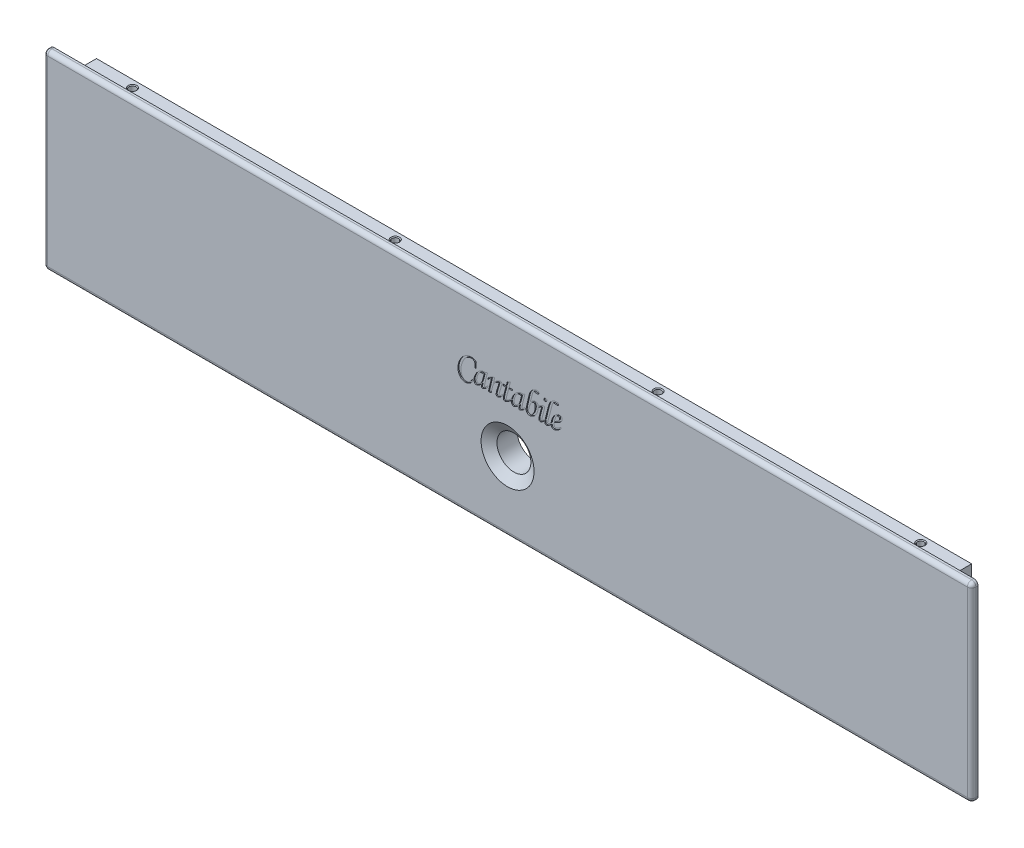
SolidWorks part; units mm, degrees
material "6061 合金"
ref_plane "前基準面" through (0, 0, 0) normal (0, 0, 1) x (1, 0, 0)
ref_plane "上基準面" through (0, 0, 0) normal (0, 1, 0) x (1, 0, 0)
ref_plane "右基準面" through (0, 0, 0) normal (1, 0, 0) x (0, 0, -1)
sketch "草圖1" plane through (0, 0, 0) normal (0, 0, 1) x (1, 0, 0)
  line L1 (0, 0) -> (438, 0)
  line L2 (0, 0) -> (0, 90)
  line L3 (0, 90) -> (438, 90)
  line L4 (438, 0) -> (438, 90)
  dimension "D1" = 90
  dimension "D2" = 438
extrude "填料-伸長1" add sketch "草圖1" along normal blind 12.5
sketch "草圖2" plane through (0, 0, 12.5) normal (0, 0, 1) x (1, 0, 0)
  line L0 (219, 90) -> (219, 0) construction
  line L1 (194, 55) -> (244, 55)
  line L2 (203.995, 61.3461) -> (203.6777, 61.3461)
  line L3 (208.9287, 62.2062) -> (209.5262, 62.2831)
  line L4 (438, 90) -> (0, 90) construction
  line L5 (0, 0) -> (438, 0) construction
  line L6 (209.5262, 62.2831) -> (208.9461, 60.171)
  line L7 (209.5683, 57.0625) -> (209.8286, 56.5865)
  line L8 (206.6977, 55.585) -> (207.0224, 56.708)
  line L9 (208.7329, 61.946) -> (208.9287, 62.2062)
  line L10 (207.248, 58.349) -> (207.9223, 60.937)
  line L11 (209.8391, 59.7595) -> (209.6805, 60.2355)
  line L12 (212.7915, 61.4725) -> (212.3974, 59.8066)
  line L13 (216.614, 57.0625) -> (216.7727, 56.5865)
  line L14 (211.909, 57.8904) -> (211.2496, 55)
  line L16 (210.5431, 57.3798) -> (211.267, 60.5305)
  line L17 (218.8581, 63.3242) -> (220.3231, 63.9365)
  line L18 (220.3231, 63.9365) -> (219.691, 61.5047)
  line L19 (219.691, 61.5047) -> (221.337, 61.5047)
  line L20 (221.337, 61.5047) -> (221.2031, 60.8701)
  line L21 (221.2031, 60.8701) -> (219.5274, 60.8701)
  line L22 (219.5274, 60.8701) -> (218.8011, 58.0565)
  line L23 (220.8685, 57.3798) -> (220.9306, 57.2873)
  line L24 (217.3732, 57.5855) -> (218.2235, 60.8701)
  line L25 (218.2235, 60.8701) -> (216.8675, 60.8701)
  line L26 (216.8675, 60.8701) -> (217.0187, 61.5047)
  line L27 (217.0187, 61.5047) -> (218.3871, 61.5047)
  line L28 (218.3871, 61.5047) -> (218.8581, 63.3242)
  line L29 (226.588, 62.2062) -> (227.1854, 62.2831)
  line L30 (227.1854, 62.2831) -> (226.6054, 60.171)
  line L31 (227.2276, 57.0625) -> (227.4879, 56.5865)
  line L32 (224.357, 55.585) -> (224.6817, 56.708)
  line L33 (226.3922, 61.946) -> (226.588, 62.2062)
  line L34 (224.9073, 58.349) -> (225.5816, 60.937)
  line L35 (227.9967, 58.0193) -> (228.9833, 62.3748)
  line L36 (230.5252, 63.4531) -> (229.7269, 60.5652)
  line L38 (236.6165, 57.0625) -> (236.7645, 56.8404)
  line L40 (237.1005, 58.2796) -> (238.0053, 61.9509)
  line L41 (239.4853, 62.2112) -> (238.5259, 58.706)
  line L42 (244.1587, 57.3798) -> (244.3173, 56.9038)
  spline S0 degree 3 poles (203.6777, 61.3461) (203.6869, 61.5436) (203.713, 61.8935) (203.7191, 62.2442) (203.7199, 62.3971) knots 0 0 0 0 0.563975 1 1 1 1
  spline S1 degree 3 poles (203.7199, 62.3971) (203.7216, 62.5802) (203.7059, 62.8446) (203.653, 63.1802) (203.5959, 63.3992) (203.5243, 63.5962) (203.4387, 63.7718) (203.3326, 63.9234) (203.1711, 64.0928) (202.9407, 64.2652) (202.5157, 64.4699) (202.1562, 64.5178) (201.9152, 64.5191) knots 0 0 0 0 0.172384 0.248892 0.319676 0.385167 0.446073 0.503069 0.558673 0.665913 0.772077 1 1 1 1
  spline S2 degree 3 poles (201.9152, 64.5191) (201.7386, 64.5211) (201.4711, 64.4906) (201.1179, 64.4056) (200.8471, 64.3153) (200.5736, 64.2019) (200.3003, 64.0577) (200.022, 63.892) (199.7429, 63.6994) (199.4678, 63.4792) (199.2024, 63.23) (198.9449, 62.9538) (198.7016, 62.6447) (198.4625, 62.3111) (198.2376, 61.9462) (198.0185, 61.5553) (197.8162, 61.1373) (197.6287, 60.7052) (197.4648, 60.2659) (197.3255, 59.8233) (197.2105, 59.3775) (197.1254, 58.9276) (197.0367, 58.3249) (197.0154, 57.8677) (197.0144, 57.5632) knots 0 0 0 0 0.056937 0.086587 0.117226 0.14905 0.182118 0.216953 0.253601 0.291576 0.330666 0.371084 0.413435 0.45765 0.503568 0.55184 0.602334 0.653503 0.703924 0.75373 0.803318 0.852524 0.901595 1 1 1 1
  spline S3 degree 3 poles (197.0144, 57.5632) (197.0183, 57.2838) (197.0311, 56.8751) (197.1112, 56.3531) (197.1862, 55.9976) (197.2887, 55.6691) (197.4081, 55.3636) (197.5565, 55.0877) (197.7217, 54.8357) (197.9068, 54.614) (198.1048, 54.422) (198.3102, 54.2543) (198.5329, 54.125) (198.7633, 54.0172) (199.0915, 53.9185) (199.3496, 53.8889) (199.5231, 53.8894) knots 0 0 0 0 0.16873 0.245832 0.318263 0.387619 0.453137 0.515781 0.57618 0.634562 0.689538 0.742383 0.794003 0.844402 0.895476 1 1 1 1
  spline S4 degree 3 poles (199.5231, 53.8894) (199.766, 53.8901) (200.1345, 53.95) (200.5971, 54.1468) (200.9381, 54.3563) (201.2723, 54.6212) (201.7208, 55.0762) (202.0191, 55.4753) (202.2077, 55.7635) knots 0 0 0 0 0.213228 0.323521 0.439808 0.563845 0.697314 1 1 1 1
  spline S5 degree 3 poles (202.2077, 55.7635) (202.243, 55.8154) (202.3119, 55.9064) (202.4175, 55.9517) (202.4655, 55.9519) knots 0 0 0 0 0.573989 1 1 1 1
  spline S6 degree 3 poles (202.4655, 55.9519) (202.5353, 55.9572) (202.6597, 55.8985) (202.7272, 55.779) (202.7258, 55.7139) knots 0 0 0 0 0.518425 1 1 1 1
  spline S7 degree 3 poles (202.7258, 55.7139) (202.7276, 55.664) (202.6982, 55.5859) (202.6472, 55.474) (202.5876, 55.3672) (202.5062, 55.2497) (202.4133, 55.1151) (202.3, 54.9692) (202.1298, 54.7537) (201.8869, 54.4877) (201.5577, 54.1941) (201.1933, 53.9277) (200.8006, 53.6932) (200.3903, 53.4997) (199.8462, 53.3165) (199.427, 53.2527) (199.1512, 53.2548) knots 0 0 0 0 0.032035 0.054118 0.080826 0.112114 0.147925 0.188169 0.233315 0.328133 0.424158 0.52233 0.623993 0.723957 0.819487 1 1 1 1
  spline S8 degree 3 poles (199.1512, 53.2548) (198.8344, 53.2547) (198.3594, 53.3169) (197.7624, 53.537) (197.3362, 53.7613) (196.9431, 54.0487) (196.5907, 54.3921) (196.2898, 54.7942) (196.0793, 55.1682) (195.9342, 55.4909) (195.8444, 55.7498) (195.7638, 56.0174) (195.7005, 56.2968) (195.6467, 56.5867) (195.6028, 56.997) (195.5851, 57.3107) (195.5865, 57.5235) knots 0 0 0 0 0.152456 0.227792 0.305152 0.383399 0.461272 0.541023 0.624162 0.667232 0.711117 0.755898 0.801609 0.848866 0.897686 1 1 1 1
  spline S9 degree 3 poles (195.5865, 57.5235) (195.5852, 57.8312) (195.6189, 58.2927) (195.7124, 58.905) (195.8191, 59.3635) (195.9484, 59.8233) (196.1148, 60.2796) (196.3051, 60.737) (196.5249, 61.189) (196.7648, 61.6288) (197.0235, 62.0464) (197.2954, 62.4387) (197.584, 62.8041) (197.886, 63.1437) (198.2023, 63.4584) (198.5342, 63.7462) (198.8809, 64.0051) (199.2323, 64.2362) (199.5838, 64.4389) (199.9328, 64.6108) (200.2812, 64.7497) (200.6262, 64.8605) (201.0806, 64.9619) (201.4246, 64.9965) (201.6525, 64.995) knots 0 0 0 0 0.08771 0.131866 0.176599 0.221976 0.26807 0.315103 0.363299 0.411419 0.458009 0.503405 0.54756 0.590817 0.633001 0.674793 0.716058 0.756409 0.794753 0.831768 0.867323 0.901702 0.935053 1 1 1 1
  spline S10 degree 2 poles (201.6525, 64.995) (202.1426, 64.9931) (202.6168, 64.8686) knots 0 0 0 1 1 1
  spline S11 degree 3 poles (202.6168, 64.8686) (202.6788, 64.8506) (202.7911, 64.8118) (202.9649, 64.7408) (203.1579, 64.6688) (203.3893, 64.5751) (203.7793, 64.4201) (204.091, 64.2922) (204.3123, 64.2018) knots 0 0 0 0 0.106273 0.195443 0.309124 0.445278 0.606438 1 1 1 1
  spline S12 degree 3 poles (204.3123, 64.2018) (204.2155, 63.7372) (204.0711, 62.7882) (204.0046, 61.8307) (203.995, 61.3461) knots 0 0 0 0 0.494681 1 1 1 1
  spline S13 degree 3 poles (208.9461, 60.171) (208.8249, 59.7212) (208.5794, 58.7583) (208.3881, 57.7832) (208.2867, 57.2657) knots 0 0 0 0 0.469109 1 1 1 1
  spline S14 degree 3 poles (208.2867, 57.2657) (208.2616, 57.1303) (208.2246, 56.9365) (208.1841, 56.6907) (208.1574, 56.5365) (208.142, 56.4022) (208.1214, 56.264) (208.1166, 56.1693) (208.1156, 56.113) knots 0 0 0 0 0.354346 0.507387 0.640863 0.756593 0.855188 1 1 1 1
  spline S15 degree 3 poles (208.1156, 56.113) (208.1148, 56.0707) (208.1467, 55.9661) (208.2564, 55.9515) (208.3016, 55.9519) knots 0 0 0 0 0.475626 1 1 1 1
  spline S16 degree 3 poles (208.3016, 55.9519) (208.3578, 55.9526) (208.4905, 56.0179) (208.6091, 56.1008) (208.6808, 56.1577) knots 0 0 0 0 0.374645 1 1 1 1
  spline S17 degree 3 poles (208.6808, 56.1577) (208.843, 56.2816) (209.1518, 56.5721) (209.4362, 56.8865) (209.5683, 57.0625) knots 0 0 0 0 0.481125 1 1 1 1
  spline S18 degree 3 poles (209.8286, 56.5865) (209.6894, 56.4521) (209.4896, 56.2635) (209.2354, 56.0279) (209.0788, 55.881) (208.9385, 55.7603) (208.7984, 55.6373) (208.7034, 55.556) (208.6437, 55.5131) knots 0 0 0 0 0.362892 0.515325 0.650236 0.765564 0.86223 1 1 1 1
  spline S19 degree 3 poles (208.6437, 55.5131) (208.4829, 55.3931) (208.1625, 55.19) (207.8214, 55.0236) (207.6546, 54.9603) knots 0 0 0 0 0.529263 1 1 1 1
  spline S20 degree 2 poles (207.6546, 54.9603) (207.3656, 54.8445) (207.0547, 54.8413) knots 0 0 0 1 1 1
  spline S21 degree 3 poles (207.0547, 54.8413) (206.9485, 54.8382) (206.695, 54.8891) (206.6305, 55.1368) (206.6332, 55.238) knots 0 0 0 0 0.515503 1 1 1 1
  spline S22 degree 2 poles (206.6332, 55.238) (206.6443, 55.4153) (206.6977, 55.585) knots 0 0 0 1 1 1
  spline S23 degree 3 poles (207.0224, 56.708) (206.7888, 56.4188) (206.2617, 55.8809) (205.6602, 55.428) (205.3392, 55.2256) knots 0 0 0 0 0.494785 1 1 1 1
  spline S24 degree 3 poles (205.3392, 55.2256) (205.1599, 55.1094) (204.8095, 54.9235) (204.4205, 54.8427) (204.2411, 54.8413) knots 0 0 0 0 0.544911 1 1 1 1
  spline S25 degree 3 poles (204.2411, 54.8413) (204.0978, 54.8423) (203.8121, 54.89) (203.5885, 55.0753) (203.5098, 55.1859) knots 0 0 0 0 0.515696 1 1 1 1
  spline S26 degree 3 poles (203.5098, 55.1859) (203.3884, 55.3442) (203.2114, 55.7382) (203.166, 56.1664) (203.1652, 56.3932) knots 0 0 0 0 0.46604 1 1 1 1
  spline S27 degree 3 poles (203.1652, 56.3932) (203.1658, 56.7099) (203.2345, 57.2) (203.4226, 57.8564) (203.6222, 58.3825) (203.8686, 58.9101) (204.1627, 59.4172) (204.4904, 59.9025) (204.8577, 60.3531) (205.2458, 60.7665) (205.7722, 61.2339) (206.2027, 61.5157) (206.5019, 61.6609) knots 0 0 0 0 0.145924 0.227198 0.314843 0.405461 0.495695 0.585209 0.675529 0.76377 0.846741 1 1 1 1
  spline S28 degree 3 poles (206.5019, 61.6609) (206.7421, 61.7736) (207.3023, 61.945) (207.8867, 61.979) (208.2024, 61.9807) knots 0 0 0 0 0.455886 1 1 1 1
  spline S29 degree 2 poles (208.2024, 61.9807) (208.4689, 61.9827) (208.7329, 61.946) knots 0 0 0 1 1 1
  spline S30 degree 3 poles (207.9223, 60.937) (207.7882, 60.9633) (207.5438, 61.0101) (207.2955, 61.0294) (207.1836, 61.0288) knots 0 0 0 0 0.549927 1 1 1 1
  spline S31 degree 3 poles (207.1836, 61.0288) (206.9533, 61.03) (206.6095, 60.9826) (206.1888, 60.8059) (205.9497, 60.6542) (205.77, 60.5044) (205.6369, 60.371) (205.508, 60.2158) (205.3813, 60.0406) (205.255, 59.8461) (205.1348, 59.6284) (205.0124, 59.3941) (204.8591, 59.0549) (204.6903, 58.6179) (204.4949, 57.9116) (204.4353, 57.3702) (204.4344, 57.0129) knots 0 0 0 0 0.128949 0.191113 0.254087 0.286585 0.321891 0.359302 0.399343 0.442816 0.488978 0.538397 0.590739 0.697122 0.800195 1 1 1 1
  spline S32 degree 3 poles (204.4344, 57.0129) (204.4345, 56.8508) (204.4514, 56.6231) (204.5281, 56.3499) (204.6121, 56.2005) (204.7155, 56.0892) (204.8734, 55.9814) (205.0147, 55.9497) (205.1087, 55.9519) knots 0 0 0 0 0.343825 0.481289 0.598223 0.703609 0.800811 1 1 1 1
  spline S33 degree 3 poles (205.1087, 55.9519) (205.2052, 55.9514) (205.351, 55.9746) (205.5422, 56.0375) (205.6909, 56.1048) (205.8424, 56.1925) (205.9964, 56.2997) (206.1518, 56.427) (206.3107, 56.57) (206.4662, 56.7315) (206.6091, 56.914) (206.7448, 57.111) (206.8675, 57.3261) (206.9794, 57.5583) (207.1172, 57.8968) (207.2031, 58.1637) (207.248, 58.349) knots 0 0 0 0 0.084387 0.128646 0.176359 0.227358 0.282073 0.340852 0.403486 0.469652 0.537264 0.606657 0.679423 0.754344 0.832719 1 1 1 1
  spline S34 degree 3 poles (209.6805, 60.2355) (209.8471, 60.3986) (210.0889, 60.6341) (210.4121, 60.9222) (210.6302, 61.1092) (210.8358, 61.2733) (211.0288, 61.4144) (211.207, 61.5343) (211.4209, 61.6606) (211.6703, 61.7837) (212.0257, 61.9249) (212.2912, 61.9788) (212.4593, 61.9807) knots 0 0 0 0 0.208761 0.302012 0.387542 0.465983 0.537445 0.601455 0.658163 0.759723 0.850114 1 1 1 1
  spline S35 degree 3 poles (212.4593, 61.9807) (212.556, 61.9873) (212.7227, 61.9449) (212.8357, 61.8094) (212.8337, 61.7353) knots 0 0 0 0 0.582663 1 1 1 1
  spline S36 degree 2 poles (212.8337, 61.7353) (212.8258, 61.6019) (212.7915, 61.4725) knots 0 0 0 1 1 1
  spline S37 degree 3 poles (212.3974, 59.8066) (212.6916, 60.1313) (213.3577, 60.7661) (214.1083, 61.2981) (214.5119, 61.5568) knots 0 0 0 0 0.477368 1 1 1 1
  spline S38 degree 3 poles (214.5119, 61.5568) (214.7085, 61.6804) (215.0639, 61.8732) (215.4562, 61.9786) (215.6274, 61.9807) knots 0 0 0 0 0.577944 1 1 1 1
  spline S39 degree 3 poles (215.6274, 61.9807) (215.724, 61.9785) (215.8681, 61.9629) (216.0341, 61.8785) (216.1352, 61.7926) (216.2146, 61.6834) (216.3011, 61.5043) (216.3095, 61.3466) (216.3141, 61.2419) knots 0 0 0 0 0.255436 0.369714 0.483396 0.599466 0.721523 1 1 1 1
  spline S40 degree 2 poles (216.3141, 61.2419) (216.3079, 60.9453) (216.2372, 60.6569) knots 0 0 0 1 1 1
  spline S41 degree 3 poles (216.2372, 60.6569) (216.2062, 60.5392) (216.1513, 60.3435) (216.0705, 60.0546) (215.9854, 59.7793) (215.8881, 59.463) (215.7363, 58.9609) (215.6083, 58.5664) (215.5208, 58.2895) knots 0 0 0 0 0.147575 0.246548 0.363846 0.496983 0.647878 1 1 1 1
  spline S42 degree 3 poles (215.5208, 58.2895) (215.4368, 58.0296) (215.3218, 57.6571) (215.1885, 57.1824) (215.111, 56.8817) (215.0504, 56.6165) (214.9997, 56.3343) (214.9711, 56.1398) (214.973, 56.0213) knots 0 0 0 0 0.350276 0.499906 0.632263 0.748461 0.84864 1 1 1 1
  spline S43 degree 3 poles (214.973, 56.0213) (214.9753, 55.9666) (214.9869, 55.8349) (215.1094, 55.7916) (215.1589, 55.7933) knots 0 0 0 0 0.539207 1 1 1 1
  spline S44 degree 3 poles (215.1589, 55.7933) (215.2066, 55.7913) (215.2792, 55.82) (215.3796, 55.8701) (215.4669, 55.9325) (215.5635, 56.0096) (215.714, 56.1428) (215.8244, 56.2583) (215.9001, 56.3411) knots 0 0 0 0 0.148367 0.246375 0.35842 0.489954 0.641461 1 1 1 1
  spline S45 degree 2 poles (215.9001, 56.3411) (216.2434, 56.7153) (216.614, 57.0625) knots 0 0 0 1 1 1
  spline S46 degree 3 poles (216.7727, 56.5865) (216.526, 56.3073) (216.0163, 55.803) (215.4473, 55.3662) (215.1564, 55.1834) knots 0 0 0 0 0.520422 1 1 1 1
  spline S47 degree 3 poles (215.1564, 55.1834) (215.0014, 55.0866) (214.7234, 54.9271) (214.4126, 54.8434) (214.2764, 54.8413) knots 0 0 0 0 0.575548 1 1 1 1
  spline S48 degree 3 poles (214.2764, 54.8413) (214.18, 54.8405) (214.0347, 54.8618) (213.8719, 54.9567) (213.7679, 55.0503) (213.6908, 55.1798) (213.6146, 55.4106) (213.5967, 55.6055) (213.5997, 55.7437) knots 0 0 0 0 0.226382 0.33079 0.435749 0.54907 0.67761 1 1 1 1
  spline S49 degree 3 poles (213.5997, 55.7437) (213.6028, 55.8173) (213.6084, 55.937) (213.6347, 56.1068) (213.6628, 56.2602) (213.6936, 56.4319) (213.7372, 56.6199) (213.7865, 56.8257) (213.8438, 57.0488) (213.9082, 57.2892) (213.9804, 57.547) (214.059, 57.8226) (214.1497, 58.1142) (214.2431, 58.4245) (214.3818, 58.8732) (214.4973, 59.216) (214.5714, 59.4522) knots 0 0 0 0 0.057567 0.09343 0.134061 0.179368 0.22962 0.28471 0.34465 0.40945 0.479117 0.553658 0.633264 0.717567 0.806756 1 1 1 1
  spline S50 degree 3 poles (214.5714, 59.4522) (214.6117, 59.6101) (214.6815, 59.8298) (214.7496, 60.11) (214.793, 60.2772) (214.8241, 60.4173) (214.8562, 60.5474) (214.8655, 60.6336) (214.8689, 60.6817) knots 0 0 0 0 0.386115 0.545633 0.682836 0.795368 0.885602 1 1 1 1
  spline S51 degree 3 poles (214.8689, 60.6817) (214.8719, 60.7381) (214.7948, 60.8686) (214.6397, 60.8632) (214.5689, 60.8701) knots 0 0 0 0 0.415072 1 1 1 1
  spline S52 degree 3 poles (214.5689, 60.8701) (214.4397, 60.8685) (214.1423, 60.7817) (213.8785, 60.6225) (213.731, 60.5231) knots 0 0 0 0 0.417811 1 1 1 1
  spline S53 degree 3 poles (213.731, 60.5231) (213.4825, 60.3568) (213.0184, 59.9901) (212.6246, 59.5486) (212.4544, 59.3133) knots 0 0 0 0 0.507554 1 1 1 1
  spline S54 degree 3 poles (212.4544, 59.3133) (212.3272, 59.136) (212.104, 58.6727) (211.9754, 58.176) (211.909, 57.8904) knots 0 0 0 0 0.425448 1 1 1 1
  spline S55 degree 2 poles (209.9507, 55) (210.2785, 56.182) (210.5431, 57.3798) knots 0 0 0 1 1 1
  spline S56 degree 2 poles (211.267, 60.5305) (211.3026, 60.666) (211.3091, 60.8057) knots 0 0 0 1 1 1
  spline S57 degree 3 poles (211.3091, 60.8057) (211.3047, 60.8577) (211.3054, 60.9852) (211.1902, 61.0302) (211.1455, 61.0288) knots 0 0 0 0 0.557559 1 1 1 1
  spline S58 degree 3 poles (211.1455, 61.0288) (211.0892, 61.025) (210.9529, 60.965) (210.8412, 60.8686) (210.7737, 60.8081) knots 0 0 0 0 0.379294 1 1 1 1
  spline S59 degree 3 poles (210.7737, 60.8081) (210.6023, 60.6605) (210.2663, 60.3308) (209.9818, 59.9561) (209.8391, 59.7595) knots 0 0 0 0 0.482081 1 1 1 1
  spline S60 degree 3 poles (218.8011, 58.0565) (218.736, 57.8711) (218.6408, 57.6055) (218.5376, 57.2615) (218.4745, 57.0396) (218.4277, 56.8401) (218.3826, 56.6221) (218.367, 56.468) (218.3648, 56.3733) knots 0 0 0 0 0.337875 0.484843 0.61755 0.73437 0.837184 1 1 1 1
  spline S61 degree 3 poles (218.3648, 56.3733) (218.3607, 56.3084) (218.3752, 56.2178) (218.4145, 56.1091) (218.5034, 55.9897) (218.6316, 55.9474) (218.7267, 55.9519) knots 0 0 0 0 0.304976 0.431392 0.54329 1 1 1 1
  spline S62 degree 3 poles (218.7267, 55.9519) (218.8429, 55.9547) (219.123, 56.0559) (219.3752, 56.2085) (219.5249, 56.3089) knots 0 0 0 0 0.388642 1 1 1 1
  spline S63 degree 2 poles (219.5249, 56.3089) (220.2392, 56.791) (220.8685, 57.3798) knots 0 0 0 1 1 1
  spline S64 degree 3 poles (220.8328, 56.6295) (220.8042, 56.6077) (220.6423, 56.4844) (220.3588, 56.2713) (219.9953, 56.0007) (219.6683, 55.7648) (219.3787, 55.5644) (219.1283, 55.3969) (218.9159, 55.2652) (218.6906, 55.1386) (218.4456, 55.0254) (218.1173, 54.8942) (217.8757, 54.8433) (217.7252, 54.8413) knots 0.110095 0.110095 0.110095 0.110095 0.136531 0.2598 0.371035 0.469889 0.556385 0.630056 0.69146 0.740166 0.820108 0.889757 1 1 1 1
  spline S65 degree 3 poles (217.7252, 54.8413) (217.6318, 54.8446) (217.4881, 54.8632) (217.3293, 54.9626) (217.2266, 55.0612) (217.1472, 55.1946) (217.0644, 55.4344) (217.0585, 55.6399) (217.0534, 55.7833) knots 0 0 0 0 0.216527 0.318216 0.423708 0.539003 0.669201 1 1 1 1
  spline S66 degree 3 poles (217.0534, 55.7833) (217.0538, 55.8952) (217.0659, 56.0725) (217.0979, 56.321) (217.1332, 56.5366) (217.1768, 56.7718) (217.2593, 57.1234) (217.3218, 57.3975) (217.3732, 57.5855) knots 0 0 0 0 0.182803 0.290405 0.409479 0.540134 0.681425 1 1 1 1
  spline S67 degree 3 poles (226.6054, 60.171) (226.4841, 59.7212) (226.2387, 58.7583) (226.0473, 57.7832) (225.946, 57.2657) knots 0 0 0 0 0.469109 1 1 1 1
  spline S68 degree 3 poles (225.946, 57.2657) (225.9208, 57.1303) (225.8839, 56.9365) (225.8433, 56.6907) (225.8166, 56.5365) (225.8013, 56.4022) (225.7807, 56.264) (225.7759, 56.1693) (225.7749, 56.113) knots 0 0 0 0 0.354346 0.507387 0.640863 0.756593 0.855188 1 1 1 1
  spline S69 degree 3 poles (225.7749, 56.113) (225.7741, 56.0707) (225.8059, 55.9661) (225.9157, 55.9515) (225.9608, 55.9519) knots 0 0 0 0 0.475626 1 1 1 1
  spline S70 degree 3 poles (225.9608, 55.9519) (226.0171, 55.9526) (226.1498, 56.0179) (226.2684, 56.1008) (226.3401, 56.1577) knots 0 0 0 0 0.374645 1 1 1 1
  spline S71 degree 3 poles (226.3401, 56.1577) (226.5022, 56.2816) (226.8111, 56.5721) (227.0955, 56.8865) (227.2276, 57.0625) knots 0 0 0 0 0.481125 1 1 1 1
  spline S72 degree 3 poles (227.4879, 56.5865) (227.3487, 56.4521) (227.1489, 56.2635) (226.8946, 56.0279) (226.738, 55.881) (226.5978, 55.7603) (226.4577, 55.6373) (226.3627, 55.556) (226.3029, 55.5131) knots 0 0 0 0 0.362892 0.515325 0.650236 0.765564 0.86223 1 1 1 1
  spline S73 degree 3 poles (226.3029, 55.5131) (226.1422, 55.3931) (225.8217, 55.19) (225.4807, 55.0236) (225.3138, 54.9603) knots 0 0 0 0 0.529263 1 1 1 1
  spline S74 degree 2 poles (225.3138, 54.9603) (225.0249, 54.8445) (224.7139, 54.8413) knots 0 0 0 1 1 1
  spline S75 degree 3 poles (224.7139, 54.8413) (224.6078, 54.8382) (224.3542, 54.8891) (224.2898, 55.1368) (224.2925, 55.238) knots 0 0 0 0 0.515503 1 1 1 1
  spline S76 degree 2 poles (224.2925, 55.238) (224.3036, 55.4153) (224.357, 55.585) knots 0 0 0 1 1 1
  spline S77 degree 3 poles (224.6817, 56.708) (224.4481, 56.4188) (223.921, 55.8809) (223.3195, 55.428) (222.9985, 55.2256) knots 0 0 0 0 0.494785 1 1 1 1
  spline S78 degree 3 poles (222.9985, 55.2256) (222.8192, 55.1094) (222.4688, 54.9235) (222.0798, 54.8427) (221.9003, 54.8413) knots 0 0 0 0 0.544911 1 1 1 1
  spline S79 degree 3 poles (221.9003, 54.8413) (221.7571, 54.8423) (221.4714, 54.89) (221.2478, 55.0753) (221.1691, 55.1859) knots 0 0 0 0 0.515696 1 1 1 1
  spline S80 degree 3 poles (221.1691, 55.1859) (221.0476, 55.3442) (220.8707, 55.7382) (220.8252, 56.1664) (220.8245, 56.3932) knots 0 0 0 0 0.46604 1 1 1 1
  spline S81 degree 2 poles (220.8245, 56.3932) (220.8248, 56.5116) (220.8328, 56.6295) knots 0 0 0 0.036362 0.036362 0.036362
  spline S82 degree 3 poles (224.1611, 61.6609) (224.4014, 61.7736) (224.9616, 61.945) (225.546, 61.979) (225.8617, 61.9807) knots 0 0 0 0 0.455886 1 1 1 1
  spline S83 degree 2 poles (225.8617, 61.9807) (226.1282, 61.9827) (226.3922, 61.946) knots 0 0 0 1 1 1
  spline S84 degree 3 poles (225.5816, 60.937) (225.4475, 60.9633) (225.2031, 61.0101) (224.9548, 61.0294) (224.8428, 61.0288) knots 0 0 0 0 0.549927 1 1 1 1
  spline S85 degree 3 poles (224.8428, 61.0288) (224.6125, 61.03) (224.2688, 60.9826) (223.8481, 60.8059) (223.609, 60.6542) (223.4292, 60.5044) (223.2962, 60.371) (223.1673, 60.2158) (223.0406, 60.0406) (222.9142, 59.8461) (222.7941, 59.6284) (222.6716, 59.3941) (222.5184, 59.0549) (222.3496, 58.6179) (222.1542, 57.9116) (222.0945, 57.3702) (222.0937, 57.0129) knots 0 0 0 0 0.128949 0.191113 0.254087 0.286585 0.321891 0.359302 0.399343 0.442816 0.488978 0.538397 0.590739 0.697122 0.800195 1 1 1 1
  spline S86 degree 3 poles (222.0937, 57.0129) (222.0938, 56.8508) (222.1107, 56.6231) (222.1874, 56.3499) (222.2714, 56.2005) (222.3748, 56.0892) (222.5327, 55.9814) (222.6739, 55.9497) (222.768, 55.9519) knots 0 0 0 0 0.343825 0.481289 0.598223 0.703609 0.800811 1 1 1 1
  spline S87 degree 3 poles (222.768, 55.9519) (222.8644, 55.9514) (223.0103, 55.9746) (223.2015, 56.0375) (223.3502, 56.1048) (223.5017, 56.1925) (223.6557, 56.2997) (223.811, 56.427) (223.97, 56.57) (224.1255, 56.7315) (224.2684, 56.914) (224.404, 57.111) (224.5268, 57.3261) (224.6387, 57.5583) (224.7764, 57.8968) (224.8623, 58.1637) (224.9073, 58.349) knots 0 0 0 0 0.084387 0.128646 0.176359 0.227358 0.282073 0.340852 0.403486 0.469652 0.537264 0.606657 0.679423 0.754344 0.832719 1 1 1 1
  spline S88 degree 3 poles (229.7269, 60.5652) (229.9345, 60.7911) (230.2528, 61.1027) (230.7122, 61.4426) (231.0384, 61.6398) (231.3562, 61.7863) (231.7336, 61.9314) (232.0199, 61.9766) (232.2009, 61.9807) knots 0 0 0 0 0.315193 0.455321 0.585804 0.70571 0.814121 1 1 1 1
  spline S89 degree 3 poles (232.2009, 61.9807) (232.3789, 61.979) (232.6528, 61.9306) (232.9519, 61.725) (233.1086, 61.5568) (233.2166, 61.3968) (233.2876, 61.2585) (233.3469, 61.1054) (233.397, 60.939) (233.4319, 60.7625) (233.4489, 60.6417) (233.4559, 60.5818) knots 0 0 0 0 0.212525 0.316137 0.42476 0.482534 0.544207 0.608313 0.676692 0.749574 0.821001 0.821001 0.821001 0.821001
  spline S90 degree 3 poles (233.48, 60.1027) (233.4796, 59.999) (233.4727, 59.7833) (233.4435, 59.456) (233.3944, 59.1223) (233.3239, 58.7906) (233.2352, 58.4599) (233.123, 58.132) (232.9935, 57.805) (232.8465, 57.4839) (232.6835, 57.1732) (232.5102, 56.8789) (232.3299, 56.6015) (232.1359, 56.3471) (231.9345, 56.11) (231.7241, 55.8914) (231.5032, 55.6922) (231.2729, 55.5155) (231.0411, 55.3561) (230.8073, 55.2205) (230.5772, 55.1025) (230.3473, 55.0081) (230.1191, 54.9323) (229.8179, 54.8647) (229.5901, 54.8395) (229.4394, 54.8413) knots 0.003602 0.003602 0.003602 0.003602 0.04638 0.092581 0.139103 0.185434 0.232403 0.280266 0.328311 0.377428 0.425915 0.472978 0.518265 0.562308 0.604865 0.646572 0.687366 0.727458 0.766223 0.803348 0.838869 0.8728 0.905787 0.937955 1 1 1 1
  spline S91 degree 3 poles (229.4394, 54.8413) (229.2079, 54.8393) (228.8662, 54.8877) (228.4651, 55.0818) (228.2147, 55.276) (228.0163, 55.5178) (227.8184, 55.8961) (227.7654, 56.2196) (227.7686, 56.4378) knots 0 0 0 0 0.267777 0.38976 0.510707 0.630615 0.74792 1 1 1 1
  spline S92 degree 3 poles (227.7686, 56.4378) (227.771, 56.6653) (227.8231, 57.1972) (227.9314, 57.7203) (227.9967, 58.0193) knots 0 0 0 0 0.426101 1 1 1 1
  spline S93 degree 3 poles (228.9833, 62.3748) (229.0412, 62.6319) (229.128, 63.007) (229.2655, 63.4862) (229.3768, 63.809) (229.4859, 64.1099) (229.6056, 64.3849) (229.7288, 64.6361) (229.9001, 64.9361) (230.1384, 65.2778) (230.4715, 65.6409) (230.8425, 65.9644) (231.2509, 66.2343) (231.6712, 66.4553) (232.2113, 66.6694) (232.6295, 66.7386) (232.9, 66.7402) knots 0 0 0 0 0.124287 0.181505 0.234984 0.285289 0.332412 0.376327 0.417167 0.495217 0.572175 0.648971 0.726783 0.802426 0.872619 1 1 1 1
  spline S94 degree 3 poles (232.9, 66.7402) (233.0358, 66.743) (233.2271, 66.7251) (233.4549, 66.6489) (233.5817, 66.5711) (233.679, 66.4747) (233.7725, 66.3214) (233.8001, 66.1868) (233.7973, 66.0957) knots 0 0 0 0 0.325937 0.456378 0.573024 0.679577 0.781934 1 1 1 1
  spline S95 degree 3 poles (233.7973, 66.0957) (233.7967, 66.0123) (233.7758, 65.8864) (233.6937, 65.7397) (233.6086, 65.6456) (233.5027, 65.5676) (233.3265, 65.4861) (233.1737, 65.4746) (233.071, 65.471) knots 0 0 0 0 0.233161 0.346527 0.463913 0.584088 0.710788 1 1 1 1
  spline S96 degree 3 poles (233.071, 65.471) (232.9516, 65.4738) (232.6492, 65.4997) (232.3503, 65.552) (232.1687, 65.5801) knots 0 0 0 0 0.393702 1 1 1 1
  spline S97 degree 2 poles (232.1687, 65.5801) (231.9179, 65.6266) (231.663, 65.6296) knots 0 0 0 1 1 1
  spline S98 degree 3 poles (231.663, 65.6296) (231.5362, 65.6325) (231.2636, 65.5443) (231.0935, 65.3144) (231.0234, 65.1884) knots 0 0 0 0 0.462467 1 1 1 1
  spline S99 degree 3 poles (231.0234, 65.1884) (230.9853, 65.1122) (230.9298, 64.9787) (230.8667, 64.7737) (230.8033, 64.5739) (230.7396, 64.3405) (230.6464, 63.9634) (230.5708, 63.665) (230.5252, 63.4531) knots 0 0 0 0 0.141377 0.239355 0.355565 0.489267 0.64055 1 1 1 1
  spline S100 degree 3 poles (231.3011, 61.0288) (231.1522, 61.0284) (230.921, 60.9449) (230.63, 60.7472) (230.4238, 60.5765) (230.2543, 60.4049) (230.1253, 60.2465) (229.9966, 60.0667) (229.8729, 59.8609) (229.75, 59.6328) (229.6245, 59.3829) (229.508, 59.1065) (229.3493, 58.7145) (229.1796, 58.2097) (228.9849, 57.4035) (228.9247, 56.7915) (228.9238, 56.3882) knots 0 0 0 0 0.079247 0.129939 0.189899 0.223709 0.260212 0.300262 0.343178 0.389968 0.440327 0.494367 0.55212 0.668981 0.782023 1 1 1 1
  spline S101 degree 3 poles (228.9238, 56.3882) (228.9238, 56.2675) (228.9554, 56.0862) (229.0705, 55.8722) (229.1901, 55.7352) (229.3296, 55.6221) (229.5351, 55.5093) (229.7086, 55.4766) (229.8236, 55.476) knots 0 0 0 0 0.254952 0.379788 0.508404 0.636129 0.757068 1 1 1 1
  spline S102 degree 3 poles (229.8236, 55.476) (229.9691, 55.4743) (230.1879, 55.5269) (230.4583, 55.6713) (230.6537, 55.8324) (230.8461, 56.0321) (231.0287, 56.2786) (231.2068, 56.5676) (231.3759, 56.8939) (231.5309, 57.2424) (231.6692, 57.5966) (231.7911, 57.9495) (231.8832, 58.304) (231.9585, 58.6571) (232.0317, 59.1248) (232.0532, 59.478) (232.0522, 59.7124) knots 0 0 0 0 0.084359 0.129295 0.178087 0.231703 0.291 0.356926 0.429928 0.505579 0.579736 0.652116 0.723563 0.793645 0.863031 1 1 1 1
  spline S103 degree 3 poles (232.0522, 59.7124) (232.0554, 59.9076) (232.0168, 60.2707) (231.888, 60.6134) (231.7944, 60.7536) knots 0 0 0 0 0.538183 1 1 1 1
  spline S104 degree 3 poles (231.7944, 60.7536) (231.7416, 60.8377) (231.5969, 60.9821) (231.3982, 61.0305) (231.3011, 61.0288) knots 0 0 0 0 0.506388 1 1 1 1
  spline S105 degree 3 poles (236.9685, 65.6296) (237.0499, 65.6299) (237.1704, 65.6127) (237.3129, 65.5439) (237.4017, 65.4734) (237.4776, 65.3902) (237.5489, 65.2546) (237.5701, 65.1399) (237.5684, 65.062) knots 0 0 0 0 0.264172 0.386274 0.508347 0.629713 0.748273 1 1 1 1
  spline S106 degree 3 poles (237.5684, 65.062) (237.5714, 64.952) (237.5354, 64.7882) (237.4268, 64.5914) (237.3143, 64.4591) (237.1834, 64.3475) (236.9972, 64.2332) (236.8367, 64.2046) (236.733, 64.2018) knots 0 0 0 0 0.248549 0.372929 0.50756 0.640756 0.762805 1 1 1 1
  spline S107 degree 3 poles (236.733, 64.2018) (236.6545, 64.2024) (236.535, 64.2181) (236.3969, 64.2906) (236.3054, 64.3604) (236.2322, 64.4488) (236.1583, 64.5895) (236.1393, 64.7102) (236.1406, 64.7918) knots 0 0 0 0 0.252998 0.374733 0.495257 0.619097 0.738486 1 1 1 1
  spline S108 degree 3 poles (236.1406, 64.7918) (236.1382, 64.902) (236.1702, 65.0664) (236.2762, 65.2601) (236.3822, 65.388) (236.5097, 65.4932) (236.6994, 65.5997) (236.8608, 65.6316) (236.9685, 65.6296) knots 0 0 0 0 0.252525 0.375618 0.503627 0.631637 0.753067 1 1 1 1
  spline S109 degree 3 poles (233.4559, 60.5818) (233.487, 60.6128) (233.6491, 60.7719) (233.9378, 61.0345) (234.321, 61.3426) (234.6908, 61.5767) (235.0364, 61.7534) (235.4362, 61.9174) (235.7354, 61.9796) (235.9249, 61.9807) knots 0.14155 0.14155 0.14155 0.14155 0.180645 0.343285 0.48807 0.616761 0.731327 0.832463 1 1 1 1
  spline S110 degree 3 poles (235.9249, 61.9807) (236.0067, 61.9806) (236.1243, 61.9752) (236.2645, 61.9319) (236.3477, 61.8933) (236.4132, 61.843) (236.4795, 61.7664) (236.4972, 61.6915) (236.4975, 61.6435) knots 0 0 0 0 0.333919 0.470765 0.593759 0.703769 0.80382 1 1 1 1
  spline S111 degree 3 poles (236.4975, 61.6435) (236.4953, 61.5689) (236.4671, 61.4347) (236.4263, 61.2229) (236.3697, 60.9911) (236.297, 60.71) (236.1788, 60.2339) (236.0708, 59.8557) (235.9993, 59.586) knots 0 0 0 0 0.105346 0.193692 0.305511 0.443147 0.604904 1 1 1 1
  spline S112 degree 3 poles (235.9993, 59.586) (235.934, 59.351) (235.8411, 59.0075) (235.7255, 58.5606) (235.6467, 58.2539) (235.5714, 57.966) (235.5042, 57.6958) (235.4459, 57.4433) (235.3902, 57.2108) (235.3437, 56.9964) (235.3007, 56.8009) (235.2661, 56.6232) (235.2389, 56.4636) (235.2166, 56.3222) (235.1945, 56.1715) (235.1857, 56.067) (235.1862, 56.004) knots 0 0 0 0 0.198986 0.290208 0.376525 0.457285 0.532973 0.603601 0.668672 0.728036 0.782502 0.831941 0.875711 0.914606 0.948636 1 1 1 1
  spline S113 degree 3 poles (235.1862, 56.004) (235.1843, 55.9496) (235.2174, 55.8485) (235.3089, 55.7943) (235.3547, 55.7933) knots 0 0 0 0 0.548845 1 1 1 1
  spline S114 degree 3 poles (235.3547, 55.7933) (235.4201, 55.7992) (235.5192, 55.8636) (235.6598, 55.9799) (235.8053, 56.1203) (235.976, 56.2986) (236.2528, 56.6141) (236.468, 56.8738) (236.6165, 57.0625) knots 0 0 0 0 0.105364 0.192097 0.303636 0.440377 0.601619 1 1 1 1
  spline S115 degree 3 poles (236.6677, 56.3299) (236.6639, 56.3262) (236.5747, 56.2408) (236.4073, 56.0824) (236.1687, 55.8665) (235.9498, 55.6747) (235.7508, 55.5065) (235.5702, 55.3643) (235.4079, 55.25) (235.2265, 55.1309) (235.0206, 55.0191) (234.7374, 54.8974) (234.5296, 54.8421) (234.3979, 54.8413) knots 0.118005 0.118005 0.118005 0.118005 0.123117 0.236192 0.33871 0.431237 0.514924 0.588211 0.651222 0.704995 0.795998 0.875068 1 1 1 1
  spline S116 degree 3 poles (234.3979, 54.8413) (234.3084, 54.8387) (234.1795, 54.8609) (234.0241, 54.9287) (233.9284, 55.0014) (233.8539, 55.095) (233.7768, 55.2443) (233.7601, 55.3741) (233.7608, 55.4611) knots 0 0 0 0 0.265717 0.384845 0.502666 0.620074 0.739126 1 1 1 1
  spline S117 degree 3 poles (233.7608, 55.4611) (233.7604, 55.5648) (233.7757, 55.7309) (233.8021, 55.9683) (233.8392, 56.181) (233.88, 56.4185) (233.9325, 56.6788) (233.9962, 56.9625) (234.0629, 57.2709) (234.1476, 57.6012) (234.2356, 57.9562) (234.3349, 58.3346) (234.4442, 58.737) (234.5638, 59.1622) (234.7354, 59.7784) (234.8791, 60.2492) (234.973, 60.5726) knots 0 0 0 0 0.059021 0.095069 0.13611 0.182032 0.232469 0.287442 0.347779 0.412324 0.481783 0.556271 0.635342 0.719454 0.808029 1 1 1 1
  spline S118 degree 2 poles (234.973, 60.5726) (235.0249, 60.7399) (235.03, 60.9147) knots 0 0 0 1 1 1
  spline S119 degree 3 poles (235.03, 60.9147) (235.0278, 60.8927) (234.9655, 60.8743) (234.912, 60.8679) (234.8689, 60.8701) knots 0 0 0 0 0.307603 1 1 1 1
  spline S120 degree 3 poles (234.8689, 60.8701) (234.7258, 60.8667) (234.563, 60.8157) (234.3871, 60.7238) (234.3032, 60.6755) (234.204, 60.6114) (234.0853, 60.5338) (233.951, 60.4393) (233.7957, 60.3334) (233.6382, 60.2178) (233.531, 60.1391) (233.48, 60.1027) knots 0 0 0 0 0.257737 0.303374 0.360511 0.43336 0.517843 0.618153 0.73137 0.859231 0.972907 0.972907 0.972907 0.972907
  spline S121 degree 3 poles (239.5738, 56.1333) (239.4482, 56.0229) (239.1764, 55.7966) (238.816, 55.5358) (238.5159, 55.3332) (238.2963, 55.206) (238.0913, 55.0908) (237.8923, 55.0039) (237.7068, 54.929) (237.4793, 54.8654) (237.3109, 54.8412) (237.2022, 54.8413) knots 0.28369 0.28369 0.28369 0.28369 0.414514 0.560262 0.631634 0.697723 0.758768 0.81549 0.867482 0.915175 1 1 1 1
  spline S122 degree 3 poles (237.2022, 54.8413) (237.1179, 54.8417) (236.9911, 54.8625) (236.8437, 54.945) (236.7491, 55.0305) (236.6711, 55.137) (236.601, 55.3151) (236.5754, 55.4605) (236.5799, 55.5627) knots 0 0 0 0 0.236438 0.35028 0.468157 0.590702 0.716071 1 1 1 1
  spline S123 degree 3 poles (236.5799, 55.5627) (236.5802, 55.7022) (236.6025, 55.9328) (236.6431, 56.1872) (236.6632, 56.3039) (236.6677, 56.3299) knots 0 0 0 0 0.150843 0.250429 0.278997 0.278997 0.278997 0.278997
  spline S124 degree 3 poles (238.0053, 61.9509) (238.0814, 62.2567) (238.1938, 62.6941) (238.3503, 63.2474) (238.4563, 63.6021) (238.5576, 63.9152) (238.6735, 64.2543) (238.7693, 64.4833) (238.8358, 64.6207) knots 0 0 0 0 0.337598 0.483908 0.616122 0.734284 0.83649 1 1 1 1
  spline S125 degree 3 poles (238.8358, 64.6207) (238.9197, 64.7861) (239.0629, 65.0228) (239.2847, 65.3133) (239.459, 65.5183) (239.6533, 65.7032) (239.8543, 65.8814) (240.0749, 66.0387) (240.3794, 66.2334) (240.7806, 66.4328) (241.4431, 66.6723) (241.9671, 66.7397) (242.3137, 66.7402) knots 0 0 0 0 0.12996 0.193184 0.255981 0.318213 0.381011 0.444008 0.507773 0.634125 0.756997 1 1 1 1
  spline S126 degree 3 poles (242.3137, 66.7402) (242.421, 66.7356) (242.5821, 66.7266) (242.7675, 66.641) (242.8798, 66.5616) (242.9709, 66.4668) (243.0574, 66.3231) (243.0873, 66.2004) (243.0847, 66.118) knots 0 0 0 0 0.294629 0.424934 0.548603 0.665838 0.77838 1 1 1 1
  spline S127 degree 3 poles (243.0847, 66.118) (243.0824, 66.0312) (243.0653, 65.8988) (242.9801, 65.748) (242.8995, 65.6476) (242.7925, 65.5669) (242.6111, 65.4858) (242.4544, 65.4748) (242.3484, 65.471) knots 0 0 0 0 0.237772 0.350034 0.466184 0.584453 0.709766 1 1 1 1
  spline S128 degree 3 poles (242.3484, 65.471) (242.2528, 65.4703) (242.0292, 65.4944) (241.8079, 65.5325) (241.6816, 65.5602) knots 0 0 0 0 0.424661 1 1 1 1
  spline S129 degree 2 poles (241.6816, 65.5602) (241.3352, 65.6269) (240.9825, 65.6296) knots 0 0 0 1 1 1
  spline S130 degree 3 poles (240.9825, 65.6296) (240.8875, 65.6339) (240.7165, 65.6096) (240.5547, 65.5446) (240.4967, 65.4908) knots 0 0 0 0 0.549369 1 1 1 1
  spline S131 degree 3 poles (240.4967, 65.4908) (240.4021, 65.4084) (240.2919, 65.2287) (240.1697, 64.9451) (240.0954, 64.7113) (240.0314, 64.4865) (239.9753, 64.2739) (239.9097, 64.0232) (239.8424, 63.733) (239.762, 63.4063) (239.6399, 62.8953) (239.5518, 62.4917) (239.4853, 62.2112) knots 0 0 0 0 0.107308 0.18079 0.267573 0.319737 0.383525 0.458254 0.544455 0.641776 0.750051 1 1 1 1
  spline S132 degree 3 poles (238.5259, 58.706) (238.4805, 58.5118) (238.4047, 58.2323) (238.3167, 57.8698) (238.2579, 57.6257) (238.1989, 57.401) (238.1518, 57.1926) (238.1026, 57.0051) (238.0644, 56.8349) (238.0262, 56.6842) (237.9946, 56.5502) (237.9661, 56.4349) (237.948, 56.3375) (237.9294, 56.2603) (237.9156, 56.1934) (237.9079, 56.1521) (237.9062, 56.1304) knots 0 0 0 0 0.225786 0.3279 0.422299 0.510116 0.590904 0.664199 0.729557 0.78833 0.840296 0.885457 0.922706 0.95244 0.975377 1 1 1 1
  spline S133 degree 3 poles (237.9062, 56.1304) (237.9071, 56.0687) (237.9212, 55.9319) (238.0449, 55.8737) (238.0995, 55.88) knots 0 0 0 0 0.550043 1 1 1 1
  spline S134 degree 3 poles (238.0995, 55.88) (238.1794, 55.881) (238.3683, 55.9518) (238.5379, 56.0565) (238.6375, 56.1254) knots 0 0 0 0 0.393578 1 1 1 1
  spline S135 degree 3 poles (238.6375, 56.1254) (238.8856, 56.2967) (239.2001, 56.5499) (239.4978, 56.8218) (239.5719, 56.8916) knots 0 0 0 0 0.476676 0.637662 0.637662 0.637662 0.637662
  spline S136 degree 3 poles (244.3173, 56.9038) (244.0014, 56.5867) (243.5271, 56.1502) (242.8729, 55.6508) (242.4216, 55.359) (241.9888, 55.1295) (241.4552, 54.9186) (241.048, 54.8416) (240.7848, 54.8413) knots 0 0 0 0 0.320963 0.461373 0.589556 0.705887 0.812054 1 1 1 1
  spline S137 degree 3 poles (240.7848, 54.8413) (240.606, 54.8399) (240.3422, 54.8832) (240.0409, 55.054) (239.8601, 55.2342) (239.7189, 55.4695) (239.6253, 55.7636) (239.5879, 55.9913) (239.575, 56.1208) (239.5738, 56.1333) knots 0 0 0 0 0.228524 0.3319 0.436954 0.550436 0.678385 0.828048 0.844102 0.844102 0.844102 0.844102
  spline S138 degree 3 poles (239.5719, 56.8916) (239.5729, 56.9072) (239.5841, 57.0706) (239.6179, 57.3811) (239.7077, 57.8204) (239.8261, 58.2586) (239.9781, 58.6981) (240.2336, 59.2897) (240.4711, 59.7193) (240.646, 60) knots 0.105566 0.105566 0.105566 0.105566 0.11823 0.237783 0.357553 0.479958 0.604284 0.732852 1 1 1 1
  spline S139 degree 3 poles (240.646, 60) (240.8392, 60.3029) (241.1393, 60.7337) (241.6189, 61.2069) (241.9787, 61.4894) (242.354, 61.7104) (242.877, 61.9178) (243.293, 61.984) (243.5711, 61.9807) knots 0 0 0 0 0.292121 0.422945 0.54523 0.662382 0.774908 1 1 1 1
  spline S140 degree 3 poles (243.5711, 61.9807) (243.7481, 61.9818) (244.0035, 61.9542) (244.3059, 61.8293) (244.4816, 61.6996) (244.6246, 61.5427) (244.7583, 61.2815) (244.7954, 61.0593) (244.7933, 60.9073) knots 0 0 0 0 0.288382 0.411173 0.527541 0.640796 0.753186 1 1 1 1
  spline S141 degree 3 poles (244.7933, 60.9073) (244.7953, 60.7297) (244.7435, 60.4593) (244.5878, 60.1196) (244.4209, 59.8597) (244.193, 59.5988) (243.7646, 59.2238) (243.3767, 58.9809) (243.0977, 58.8176) knots 0 0 0 0 0.188139 0.288435 0.39594 0.515568 0.655618 1 1 1 1
  spline S142 degree 3 poles (243.0977, 58.8176) (242.9973, 58.7616) (242.8285, 58.6717) (242.5762, 58.5525) (242.339, 58.4377) (242.0668, 58.311) (241.6371, 58.1134) (241.2963, 57.9605) (241.0575, 57.8557) knots 0 0 0 0 0.152871 0.254108 0.371074 0.503302 0.653256 1 1 1 1
  spline S143 degree 2 poles (241.0575, 57.8557) (240.9863, 57.4323) (240.9856, 57.003) knots 0 0 0 1 1 1
  spline S144 degree 3 poles (240.9856, 57.003) (240.9879, 56.8365) (240.9985, 56.603) (241.0814, 56.3278) (241.1678, 56.182) (241.2798, 56.0748) (241.4664, 55.9747) (241.6294, 55.9528) (241.7392, 55.9519) knots 0 0 0 0 0.337591 0.467487 0.576876 0.67608 0.776957 1 1 1 1
  spline S145 degree 3 poles (241.7392, 55.9519) (241.863, 55.9551) (242.1319, 55.9936) (242.3789, 56.107) (242.5077, 56.1725) knots 0 0 0 0 0.460659 1 1 1 1
  spline S146 degree 3 poles (242.5077, 56.1725) (242.6144, 56.2314) (242.784, 56.3295) (243.0124, 56.486) (243.2107, 56.6274) (243.4256, 56.7867) (243.7435, 57.0391) (243.9918, 57.2368) (244.1587, 57.3798) knots 0 0 0 0 0.17852 0.286601 0.405478 0.535212 0.678292 1 1 1 1
  spline S147 degree 3 poles (241.1542, 58.3317) (241.3573, 58.4285) (241.653, 58.5738) (242.0237, 58.7891) (242.2761, 58.9462) (242.5086, 59.1075) (242.7812, 59.3252) (242.9742, 59.4923) (243.0853, 59.6158) knots 0 0 0 0 0.289527 0.423345 0.551339 0.671942 0.786984 1 1 1 1
  spline S148 degree 3 poles (243.0853, 59.6158) (243.212, 59.761) (243.4352, 60.0493) (243.5239, 60.404) (243.524, 60.5677) knots 0 0 0 0 0.54378 1 1 1 1
  spline S149 degree 3 poles (243.524, 60.5677) (243.5208, 60.6748) (243.5073, 60.8337) (243.4278, 61.0218) (243.3478, 61.137) (243.2505, 61.2294) (243.1, 61.3239) (242.9656, 61.3468) (242.877, 61.3461) knots 0 0 0 0 0.284809 0.412853 0.535097 0.652375 0.764994 1 1 1 1
  spline S150 degree 3 poles (242.877, 61.3461) (242.7782, 61.3449) (242.5672, 61.3045) (242.3897, 61.1836) (242.3044, 61.113) knots 0 0 0 0 0.470604 1 1 1 1
  spline S151 degree 3 poles (242.3044, 61.113) (242.1685, 61.0047) (241.9197, 60.7156) (241.7512, 60.3744) (241.6723, 60.1859) knots 0 0 0 0 0.458219 1 1 1 1
  spline S152 degree 3 poles (241.6723, 60.1859) (241.5482, 59.8873) (241.3456, 59.276) (241.2037, 58.6479) (241.1542, 58.3317) knots 0 0 0 0 0.502495 1 1 1 1
  spline S153 degree 3 poles (220.9306, 57.2873) (220.934, 57.3024) (220.9767, 57.4893) (221.0819, 57.8564) (221.2814, 58.3825) (221.5279, 58.9101) (221.822, 59.4172) (222.1497, 59.9025) (222.517, 60.3531) (222.9051, 60.7665) (223.4314, 61.2339) (223.862, 61.5157) (224.1611, 61.6609) knots 0.138763 0.138763 0.138763 0.138763 0.145924 0.227198 0.314843 0.405461 0.495695 0.585209 0.675529 0.76377 0.846741 1 1 1 1
  spline S154 degree 3 poles (236.7645, 56.8404) (236.7707, 56.8707) (236.8049, 57.0368) (236.911, 57.5179) (237.0233, 57.9659) (237.1005, 58.2796) knots 0.466557 0.466557 0.466557 0.466557 0.499963 0.650188 1 1 1 1
  point P9 (219, 55)
  dimension "D1" = 25
  dimension "D2" = 35
extrude "除料-伸長1" cut sketch "草圖2" against normal blind 0.5 contours S154 L38 S114 S113 S112 S111 S110 S109 S89 S88 L36 S99 S98 S97 S96 S95 S94 S93 L35 S92 S91 L1 S90 S120 S119 S118 S117 S116 S115 S123 S122 S121 S137 S136 L42 S146 S145 S144 S143 S142 S141 S140 S139 S138 S135 S134 S133 S132 | S108 S107 S106 S105 | S62 L0 S64 S81 S80 S79 L1 S78 S77 L32 S76 S75 S73 S72 L31 S71 S70 S69 S68 S67 L30 L29 L33 S83 S82 S153 L23 S63 S87 S86 S85 S84 L34 | L17 L0 L22 L21 L20 L19 L18 | L0 L17 L28 L27 L26 L25 L24 S66 S65 L1 S64 S62 S61 S60 L22 | S59 S58 S57 S56 L16 S55 L1 L14 S54 S53 S52 S51 S50 S49 S48 S47 S46 L13 S45 S44 S43 S42 S41 S40 S39 S38 S37 L12 S36 S35 S34 L11 | S48 S47 L1 | S29 S28 S27 S26 S25 L1 S24 S23 L8 S22 S21 S19 S18 L7 S17 S16 S15 S14 S13 L6 L3 L9 S33 S32 S31 S30 L10 | S25 S24 L1 | S21 S20 S19 L1 | S12 S11 S10 S9 S8 L1 S3 S2 S1 S0 L2 | S7 S6 S5 S4 L1 | S8 S7 L1 S4 S3 | S75 S74 S73 L1 | S79 S78 L1 | S65 S64 L1 | S137 S136 L1 | S122 S121 L1 | S116 S115 L1 | S91 S90 L1 region at (219.6997, 61.8261, 12.5) region at (218.1533, 58.4507, 12.5) region at (235.9065, 59.7806, 12.5) region at (229.46, 54.9359, 12.5) region at (200.8962, 53.8276, 12.5) region at (202.2721, 55.4256, 12.5) region at (207.1651, 54.9354, 12.5) region at (207.2231, 55.0987, 12.5) region at (214.3012, 54.9364, 12.5) region at (214.3295, 55.0995, 12.5) region at (219.3248, 56.0526, 12.5) region at (217.7936, 54.9368, 12.5) region at (221.9416, 54.9365, 12.5) region at (224.8244, 54.9354, 12.5) region at (234.4231, 54.9365, 12.5) region at (204.2824, 54.9365, 12.5) region at (237.2891, 54.9365, 12.5) region at (240.8555, 54.9362, 12.5) region at (196.8965, 55.1327, 12.5) region at (236.8512, 64.9199, 12.5)
hole_wizard "開關圓孔" positions "草圖4" profile "草圖3" countersink size "M2" standard "Iso" end condition through all
sketch "草圖4" plane through (0, 0, 12.5) normal (0, 0, 1) x (1, 0, 0)
  line L0 (0, 0) -> (438, 0) construction
  line L1 (438, 0) -> (438, 90) construction
  point P0 (219, 33)
  point P3 (219, 0)
  dimension "D1" = 33
  dimension "D2" = 219
sketch "草圖3" plane through (219, 33, 12.5) normal (1, 0, 0) x (0, -1, 0)
  line L0 (0, 0) -> (0, 12.5)
  line L1 (0, 12.5) -> (8, 12.5)
  line L2 (8, 12.5) -> (8, 3.0011)
  line L3 (8, 3.0011) -> (12.5, 0)
  line L5 (12.5, 0) -> (0, 0)
  line L6 (-8, 3.0011) -> (-12.5, 0) construction
  line L11 (0, -6.35) -> (0, 107.95) construction
  dimension "貫穿孔直徑" = 16
  dimension "貫穿孔深度" = 12.5
  dimension "近端錐孔直徑" = 25
  dimension "近端錐孔角度" = 112.6
sketch "草圖6" plane through (438, 0, 0) normal (1, 0, 0) x (0, 0, -1)
  line L0 (-12.5, 0) -> (-12.5, 90) construction
  line L1 (0, 90) -> (-9.5, 90)
  line L2 (0, 90) -> (0, 86)
  line L3 (0, 86) -> (-9.5, 86)
  line L4 (-9.5, 90) -> (-9.5, 86)
  line L5 (0, 0) -> (-9.5, 0)
  line L6 (0, 0) -> (0, 4)
  line L7 (0, 4) -> (-9.5, 4)
  line L8 (-9.5, 0) -> (-9.5, 4)
  dimension "D1" = 3
  dimension "D2" = 3
  dimension "D3" = 4
  dimension "D4" = 4
sketch "草圖5" plane through (0, 90, 0) normal (0, 1, 0) x (1, 0, 0)
  line L0 (438, -12.5) -> (0, -12.5) construction
  line L1 (438, 0) -> (425.5, 0)
  line L2 (438, 0) -> (438, -9.5)
  line L3 (438, -9.5) -> (425.5, -9.5)
  line L4 (425.5, 0) -> (425.5, -9.5)
  line L5 (0, 0) -> (12.5, 0)
  line L6 (0, 0) -> (0, -9.5)
  line L7 (0, -9.5) -> (12.5, -9.5)
  line L8 (12.5, 0) -> (12.5, -9.5)
  dimension "D1" = 12.5
  dimension "D2" = 3
  dimension "D3" = 3
  dimension "D4" = 12.5
extrude "除料-伸長2" cut sketch "草圖5" against normal through all
extrude "除料-伸長3" cut sketch "草圖6" against normal through all
fillet "圓角1" radius 2 4 edges at (438, 45, 12.5) (219, 0, 12.5) (0, 45, 12.5) (219, 90, 12.5)
fillet "圓角2" radius 2 8 edges at (0.5858, 89.4142, 11.9142) (0.5858, 0.5858, 11.9142) (437.4142, 0.5858, 11.9142) (437.4142, 89.4142, 11.9142) (0, 90, 10) (0, 0, 10) (438, 0, 10) (438, 90, 10)
hole_wizard "M4 螺紋孔1" positions "草圖8" profile "草圖7" tap size "M4" standard "Iso" end condition through all
sketch "草圖8" plane through (0, 86, 0) normal (0, 1, 0) x (1, 0, 0)
  line L0 (12.5, -9.5) -> (12.5, 0) construction
  line L4 (12.5, -9.5) -> (425.5, -9.5) construction
  point P0 (33, -3.5)
  point P2 (157, -3.5)
  point P4 (281, -3.5)
  point P6 (405, -3.5)
  dimension "D1" = 20.5
  dimension "D2" = 124
  dimension "D3" = 124
  dimension "D4" = 124
  dimension "D5" = 6
cosmetic thread "鑽孔螺紋1" parameters "D2"=4
cosmetic thread "鑽孔螺紋2" parameters "D2"=4
cosmetic thread "鑽孔螺紋3" parameters "D2"=4
cosmetic thread "鑽孔螺紋4" parameters "D2"=4
sketch "草圖7" plane through (33, 86, 3.5) normal (1, 0, 0) x (0, 0, 1)
  line L0 (0, 0) -> (0, 86)
  line L1 (0, 86) -> (1.65, 86)
  line L2 (1.65, 86) -> (1.65, 0.375)
  line L3 (1.65, 0.375) -> (2.025, 0)
  line L5 (2.025, 0) -> (0, 0)
  line L6 (-1.65, 0.375) -> (-2.025, 0) construction
  line L11 (0, -6.35) -> (0, 107.95) construction
  dimension "貫穿螺孔鑽直徑" = 3.3
  dimension "貫穿螺孔鑽深度" = 86
  dimension "近端錐孔直徑" = 4.05
  dimension "近端錐孔角度" = 90
hole_wizard "M4 螺紋孔2" positions "草圖10" profile "草圖9" tap size "M4" standard "Iso"
sketch "草圖10" plane through (12.5, 0, 0) normal (-1, 0, 0) x (0, 0, 1)
  line L0 (9.5, 86) -> (0, 86) construction
  line L1 (0, 4) -> (9.5, 4) construction
  line L2 (9.5, 4) -> (9.5, 86) construction
  point P0 (3.5, 70)
  point P2 (3.5, 20)
  dimension "D1" = 16
  dimension "D2" = 16
  dimension "D3" = 6
sketch "草圖9" plane through (12.5, 70, 3.5) normal (0, 1, 0) x (0, 0, 1)
  line L0 (0, 0) -> (0, 5.9914)
  line L1 (0, 5.9914) -> (1.65, 5)
  line L2 (1.65, 5) -> (1.65, 0.375)
  line L3 (1.65, 0.375) -> (2.025, 0)
  line L5 (2.025, 0) -> (0, 0)
  line L6 (-1.65, 0.375) -> (-2.025, 0) construction
  line L10 (0, 5.9914) -> (-1.65, 5) construction
  line L11 (0, -6.35) -> (0, 107.95) construction
  dimension "螺孔鑽直徑" = 3.3
  dimension "螺孔鑽深度" = 5
  dimension "近端錐孔直徑" = 4.05
  dimension "近端錐孔角度" = 90
  dimension "導頭角度" = 118
cosmetic thread "鑽孔螺紋5" parameters "D1"=5, "D2"=4
cosmetic thread "鑽孔螺紋6" parameters "D1"=5, "D2"=4
hole_wizard "M4 螺紋孔3" positions "草圖12" profile "草圖11" tap size "M4" standard "Iso"
sketch "草圖12" plane through (425.5, 0, 0) normal (1, 0, 0) x (0, 0, -1)
  line L0 (0, 86) -> (-9.5, 86) construction
  line L1 (-9.5, 4) -> (0, 4) construction
  line L2 (-9.5, 4) -> (-9.5, 86) construction
  point P0 (-3.5, 70)
  point P2 (-3.5, 20)
  dimension "D1" = 16
  dimension "D2" = 16
  dimension "D3" = 6
sketch "草圖11" plane through (425.5, 70, 3.5) normal (0, 1, 0) x (0, 0, -1)
  line L0 (0, 0) -> (0, 5.9914)
  line L1 (0, 5.9914) -> (1.65, 5)
  line L2 (1.65, 5) -> (1.65, 0.375)
  line L3 (1.65, 0.375) -> (2.025, 0)
  line L5 (2.025, 0) -> (0, 0)
  line L6 (-1.65, 0.375) -> (-2.025, 0) construction
  line L10 (0, 5.9914) -> (-1.65, 5) construction
  line L11 (0, -6.35) -> (0, 107.95) construction
  dimension "螺孔鑽直徑" = 3.3
  dimension "螺孔鑽深度" = 5
  dimension "近端錐孔直徑" = 4.05
  dimension "近端錐孔角度" = 90
  dimension "導頭角度" = 118
cosmetic thread "鑽孔螺紋7" parameters "D1"=4.3, "D2"=4
cosmetic thread "鑽孔螺紋8" parameters "D1"=4.3, "D2"=4
